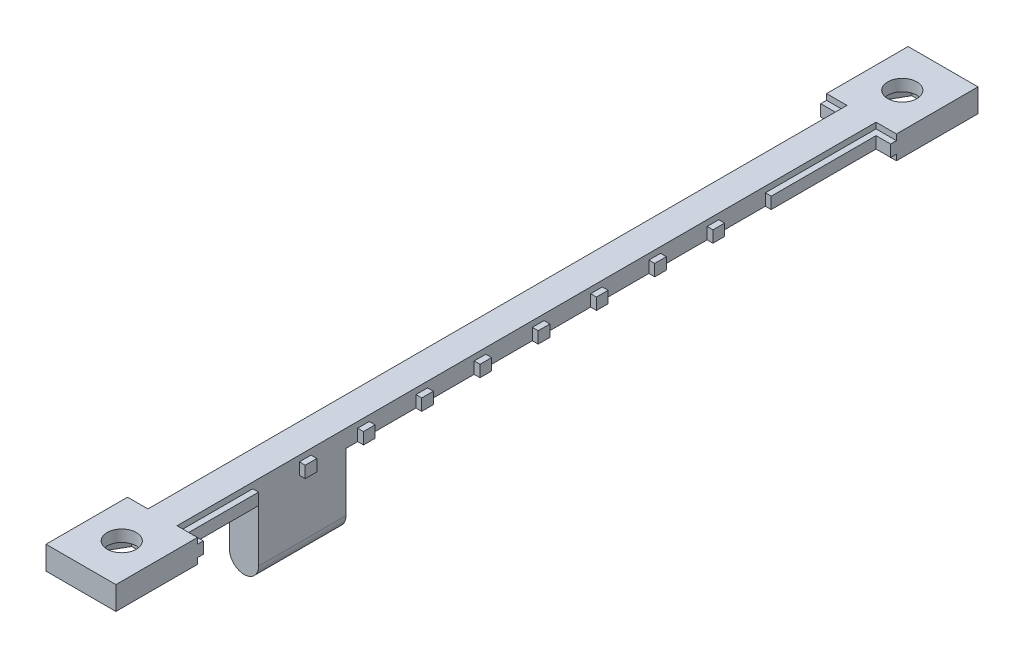
SolidWorks part; units mm, degrees
ref_plane "Front Plane" through (0, 0, 0) normal (0, 0, 1) x (1, 0, 0)
ref_plane "Top Plane" through (0, 0, 0) normal (0, 1, 0) x (1, 0, 0)
ref_plane "Right Plane" through (0, 0, 0) normal (1, 0, 0) x (0, 0, -1)
sketch "Sketch1" plane through (0, 0, 0) normal (0, 1, 0) x (1, 0, 0)
  line L0 (7.2267, 6.096) -> (7.2267, 18.096)
  line L1 (12.2267, 6.096) -> (12.2267, 18.096)
  line L2 (7.2267, 128.096) -> (3.7267, 128.096)
  line L3 (12.2267, 128.096) -> (15.7267, 128.096)
  line L4 (3.7267, 128.096) -> (3.7267, 140.096)
  line L5 (15.7267, 128.096) -> (15.7267, 140.096)
  line L6 (3.7267, 140.096) -> (15.7267, 140.096)
  line L7 (7.2267, 6.096) -> (3.7267, 6.096)
  line L8 (12.2267, 6.096) -> (15.7267, 6.096)
  line L9 (3.7267, 6.096) -> (3.7267, -5.904)
  line L10 (15.7267, 6.096) -> (15.7267, -5.904)
  line L11 (3.7267, -5.904) -> (15.7267, -5.904)
  line L12 (7.2267, 120.096) -> (7.2267, 128.096)
  line L13 (7.2267, 6.096) -> (7.2267, 128.096) construction
  line L14 (-994.5233, 128.096) -> (49005.4767, 128.096) construction
  line L15 (6.2267, 120.096) -> (7.2267, 120.096)
  line L18 (6.2267, 118.096) -> (7.2267, 118.096)
  line L19 (6.2267, 110.096) -> (7.2267, 110.096)
  line L20 (6.2267, 108.096) -> (7.2267, 108.096)
  line L21 (6.2267, 100.096) -> (7.2267, 100.096)
  line L22 (6.2267, 98.096) -> (7.2267, 98.096)
  line L23 (6.2267, 90.096) -> (7.2267, 90.096)
  line L24 (6.2267, 88.096) -> (7.2267, 88.096)
  line L25 (6.2267, 80.096) -> (7.2267, 80.096)
  line L26 (6.2267, 78.096) -> (7.2267, 78.096)
  line L27 (6.2267, 70.096) -> (7.2267, 70.096)
  line L28 (6.2267, 68.096) -> (7.2267, 68.096)
  line L29 (6.2267, 60.096) -> (7.2267, 60.096)
  line L30 (6.2267, 58.096) -> (7.2267, 58.096)
  line L31 (6.2267, 50.096) -> (7.2267, 50.096)
  line L32 (6.2267, 48.096) -> (7.2267, 48.096)
  line L33 (6.2267, 40.096) -> (7.2267, 40.096)
  line L34 (6.2267, 38.096) -> (7.2267, 38.096)
  line L35 (6.2267, 30.096) -> (7.2267, 30.096)
  line L36 (6.2267, 28.096) -> (7.2267, 28.096)
  line L37 (6.2267, 20.096) -> (7.2267, 20.096)
  line L38 (6.2267, 18.096) -> (7.2267, 18.096)
  line L39 (-994.5233, 118.096) -> (49005.4767, 118.096) construction
  line L40 (-994.5233, 120.096) -> (49005.4767, 120.096) construction
  line L41 (12.2267, 120.096) -> (12.2267, 128.096)
  line L42 (12.2267, 6.096) -> (12.2267, 128.096) construction
  line L43 (6.2267, 118.096) -> (6.2267, 120.096)
  line L44 (12.2267, 118.096) -> (13.2267, 118.096)
  line L45 (12.2267, 120.096) -> (13.2267, 120.096)
  line L46 (7.2267, 110.096) -> (7.2267, 118.096)
  line L47 (12.2267, 110.096) -> (12.2267, 118.096)
  line L48 (13.2267, 118.096) -> (13.2267, 120.096)
  line L49 (-994.5233, 110.096) -> (49005.4767, 110.096) construction
  line L50 (-994.5233, 108.096) -> (49005.4767, 108.096) construction
  line L51 (13.2267, 108.096) -> (13.2267, 110.096)
  line L52 (-994.5233, 100.096) -> (49005.4767, 100.096) construction
  line L53 (12.2267, 110.096) -> (13.2267, 110.096)
  line L54 (12.2267, 108.096) -> (13.2267, 108.096)
  line L55 (12.2267, 100.096) -> (13.2267, 100.096)
  line L56 (12.2267, 98.096) -> (13.2267, 98.096)
  line L57 (-994.5233, 98.096) -> (49005.4767, 98.096) construction
  line L58 (12.2267, 90.096) -> (13.2267, 90.096)
  line L59 (-994.5233, 90.096) -> (49005.4767, 90.096) construction
  line L60 (12.2267, 88.096) -> (13.2267, 88.096)
  line L61 (-994.5233, 88.096) -> (49005.4767, 88.096) construction
  line L62 (12.2267, 80.096) -> (13.2267, 80.096)
  line L63 (-994.5233, 80.096) -> (49005.4767, 80.096) construction
  line L64 (12.2267, 78.096) -> (13.2267, 78.096)
  line L65 (-994.5233, 78.096) -> (49005.4767, 78.096) construction
  line L66 (12.2267, 70.096) -> (13.2267, 70.096)
  line L67 (-994.5233, 70.096) -> (49005.4767, 70.096) construction
  line L68 (12.2267, 68.096) -> (13.2267, 68.096)
  line L69 (-994.5233, 68.096) -> (49005.4767, 68.096) construction
  line L70 (12.2267, 60.096) -> (13.2267, 60.096)
  line L71 (-994.5233, 60.096) -> (49005.4767, 60.096) construction
  line L72 (12.2267, 58.096) -> (13.2267, 58.096)
  line L73 (-994.5233, 58.096) -> (49005.4767, 58.096) construction
  line L74 (12.2267, 50.096) -> (13.2267, 50.096)
  line L75 (-994.5233, 50.096) -> (49005.4767, 50.096) construction
  line L76 (12.2267, 48.096) -> (13.2267, 48.096)
  line L77 (-994.5233, 48.096) -> (49005.4767, 48.096) construction
  line L78 (12.2267, 40.096) -> (13.2267, 40.096)
  line L79 (-994.5233, 40.096) -> (49005.4767, 40.096) construction
  line L80 (12.2267, 38.096) -> (13.2267, 38.096)
  line L81 (-994.5233, 38.096) -> (49005.4767, 38.096) construction
  line L82 (12.2267, 30.096) -> (13.2267, 30.096)
  line L83 (-994.5233, 30.096) -> (49005.4767, 30.096) construction
  line L84 (12.2267, 28.096) -> (13.2267, 28.096)
  line L85 (-994.5233, 28.096) -> (49005.4767, 28.096) construction
  line L86 (12.2267, 20.096) -> (13.2267, 20.096)
  line L87 (-994.5233, 20.096) -> (49005.4767, 20.096) construction
  line L88 (12.2267, 18.096) -> (13.2267, 18.096)
  line L89 (-994.5233, 18.096) -> (49005.4767, 18.096) construction
  line L90 (13.2267, 18.096) -> (13.2267, 20.096)
  line L91 (6.2267, 108.096) -> (6.2267, 110.096)
  line L92 (12.2267, 100.096) -> (12.2267, 108.096)
  line L93 (7.2267, 100.096) -> (7.2267, 108.096)
  line L94 (7.2267, 90.096) -> (7.2267, 98.096)
  line L95 (12.2267, 90.096) -> (12.2267, 98.096)
  line L96 (13.2267, 98.096) -> (13.2267, 100.096)
  line L97 (6.2267, 98.096) -> (6.2267, 100.096)
  line L98 (12.2267, 80.096) -> (12.2267, 88.096)
  line L99 (7.2267, 80.096) -> (7.2267, 88.096)
  line L100 (7.2267, 70.096) -> (7.2267, 78.096)
  line L101 (12.2267, 70.096) -> (12.2267, 78.096)
  line L102 (12.2267, 60.096) -> (12.2267, 68.096)
  line L103 (7.2267, 60.096) -> (7.2267, 68.096)
  line L104 (13.2267, 88.096) -> (13.2267, 90.096)
  line L105 (13.2267, 78.096) -> (13.2267, 80.096)
  line L106 (13.2267, 68.096) -> (13.2267, 70.096)
  line L107 (13.2267, 58.096) -> (13.2267, 60.096)
  line L108 (6.2267, 58.096) -> (6.2267, 60.096)
  line L109 (6.2267, 68.096) -> (6.2267, 70.096)
  line L110 (6.2267, 78.096) -> (6.2267, 80.096)
  line L111 (6.2267, 88.096) -> (6.2267, 90.096)
  line L112 (12.2267, 50.096) -> (12.2267, 58.096)
  line L113 (7.2267, 50.096) -> (7.2267, 58.096)
  line L114 (7.2267, 40.096) -> (7.2267, 48.096)
  line L115 (12.2267, 40.096) -> (12.2267, 48.096)
  line L116 (7.2267, 30.096) -> (7.2267, 38.096)
  line L117 (12.2267, 30.096) -> (12.2267, 38.096)
  line L118 (7.2267, 20.096) -> (7.2267, 28.096)
  line L119 (12.2267, 20.096) -> (12.2267, 28.096)
  line L120 (6.2267, 18.096) -> (6.2267, 20.096)
  line L121 (6.2267, 28.096) -> (6.2267, 30.096)
  line L122 (6.2267, 38.096) -> (6.2267, 40.096)
  line L123 (6.2267, 48.096) -> (6.2267, 50.096)
  line L124 (13.2267, 48.096) -> (13.2267, 50.096)
  line L125 (13.2267, 28.096) -> (13.2267, 30.096)
  line L126 (13.2267, 38.096) -> (13.2267, 40.096)
  point P20 (5.4767, 128.096)
  dimension "D1" = 5
  dimension "D4" = 8
  dimension "D5" = 2
  dimension "D6" = 10
  dimension "D7" = 20
  dimension "D8" = 40
  dimension "D9" = 40
extrude "Boss-Extrude1" add sketch "Sketch1" along normal blind 2
sketch "Sketch2" plane through (0, 2, 0) normal (0, 1, 0) x (1, 0, 0)
  line L0 (3.7267, 140.096) -> (15.7267, 140.096)
  line L1 (15.7267, 140.096) -> (15.7267, 128.096)
  line L2 (15.7267, 128.096) -> (12.2267, 128.096)
  line L3 (12.2267, 128.096) -> (15.7267, 128.096) construction
  line L4 (12.2267, 128.096) -> (12.2267, 6.096)
  line L5 (12.2267, 6.096) -> (15.7267, 6.096)
  line L6 (15.7267, 6.096) -> (15.7267, -5.904)
  line L7 (3.7267, -5.904) -> (15.7267, -5.904) construction
  line L8 (15.7267, -5.904) -> (15.7267, 6.096) construction
  line L9 (15.7267, -5.904) -> (3.7267, -5.904)
  line L10 (3.7267, 6.096) -> (3.7267, -5.904) construction
  line L11 (3.7267, -5.904) -> (3.7267, 6.096)
  line L12 (3.7267, 6.096) -> (7.2267, 6.096)
  line L13 (7.2267, 6.096) -> (7.2267, 128.096)
  line L14 (7.2267, 128.096) -> (3.7267, 128.096)
  line L15 (3.7267, 128.096) -> (7.2267, 128.096) construction
  line L16 (3.7267, 140.096) -> (3.7267, 128.096) construction
  line L17 (3.7267, 128.096) -> (3.7267, 140.096)
extrude "Boss-Extrude2" add sketch "Sketch2" along normal blind 1
sketch "Sketch3" plane through (0, 0, 0) normal (0, -1, 0) x (-1, 0, 0)
  line L0 (-15.7267, 128.096) -> (-3.7267, 128.096)
  line L1 (-12.2267, 128.096) -> (-15.7267, 128.096) construction
  line L2 (-15.7267, 128.096) -> (-15.7267, 140.096) construction
  line L3 (-3.7267, 128.096) -> (-3.7267, 140.096)
  line L4 (-3.7267, 140.096) -> (-3.7267, 128.096) construction
  line L5 (-15.7267, 140.096) -> (-3.7267, 140.096) construction
  line L6 (-3.7267, 140.096) -> (-15.7267, 140.096)
  line L7 (-15.7267, 140.096) -> (-15.7267, 128.096)
  line L8 (-3.7267, -5.904) -> (-3.7267, 6.096)
  line L9 (-3.7267, 6.096) -> (-15.7267, 6.096)
  line L10 (-15.7267, 6.096) -> (-15.7267, -5.904)
  line L11 (-15.7267, -5.904) -> (-3.7267, -5.904)
extrude "Boss-Extrude3" add sketch "Sketch3" along normal blind 1 contours L11 L8 L9 L10 | L7 L0 L3 L6
sketch "Sketch4" plane through (0, -1, 0) normal (0, -1, 0) x (-1, 0, 0)
  line L0 (-1015.7267, 134.096) -> (48984.2733, 134.096) construction
  line L1 (-15.7267, 140.096) -> (-15.7267, 128.096) construction
  line L2 (-9.7267, -859.904) -> (-9.7267, 49140.096) construction
  line L3 (-3.7267, 140.096) -> (-15.7267, 140.096) construction
  line L4 (-1015.7267, 0.096) -> (48984.2733, 0.096) construction
  line L11 (-7.3651, 138.096) -> (-11.9839, 138.096)
  line L12 (-11.9839, 138.096) -> (-14.2933, 134.096)
  line L13 (-14.2933, 134.096) -> (-11.9839, 130.096)
  line L14 (-11.9839, 130.096) -> (-7.3651, 130.096)
  line L15 (-7.3651, 130.096) -> (-5.0557, 134.096)
  line L16 (-5.0557, 134.096) -> (-7.3651, 138.096)
  line L17 (-15.7267, 6.096) -> (-15.7267, -5.904) construction
  line L19 (-7.4173, 4.096) -> (-12.0361, 4.096)
  line L20 (-12.0361, 4.096) -> (-14.3455, 0.096)
  line L21 (-14.3455, 0.096) -> (-12.0361, -3.904)
  line L22 (-12.0361, -3.904) -> (-7.4173, -3.904)
  line L23 (-7.4173, -3.904) -> (-5.1079, 0.096)
  line L24 (-5.1079, 0.096) -> (-7.4173, 4.096)
  circle A1 centre (-9.6745, 134.096) radius 4 construction
  circle A2 centre (-9.7267, 0.096) radius 4 construction
  point P5 (-15.7267, 134.096)
  point P10 (-9.7267, 140.096)
  point P31 (-15.7267, 0.096)
extrude "Cut-Extrude1" cut sketch "Sketch4" against normal blind 2 contours L11 L12 L13 L14 L15 L16 | L19 L20 L21 L22 L23 L24
sketch "Sketch5" plane through (0, 1, 0) normal (0, -1, 0) x (-1, 0, 0)
  line L0 (-1005.0557, 134.096) -> (48994.9443, 134.096) construction
  line L1 (-1005.1079, 0.096) -> (48994.8921, 0.096) construction
  line L2 (-9.7267, -995.904) -> (-9.7267, 49004.096) construction
  line L3 (-7.4173, 4.096) -> (-12.0361, 4.096) construction
  circle A0 centre (-9.7267, 0.096) radius 2.5
  circle A1 centre (-9.7267, 134.096) radius 2.5
  point P11 (-9.7267, 4.096)
extrude "Cut-Extrude2" cut sketch "Sketch5" against normal blind 5 contours A1 | A0
sketch "Sketch6" plane through (0, 0, 0) normal (0, -1, 0) x (-1, 0, 0)
  line L0 (-1006.1015, 6.096) -> (48993.8985, 6.096) construction
  line L2 (-1004.9212, 128.096) -> (48995.0788, 128.096) construction
  line L4 (-11.2267, 21.096) -> (-8.2267, 21.096)
  line L5 (-11.2267, 36.096) -> (-8.2267, 36.096)
  line L11 (-12.2267, 21.096) -> (-12.2267, 36.096) construction
  line L14 (-11.2267, 21.096) -> (-11.2267, 36.096)
  line L16 (-8.2267, 21.096) -> (-8.2267, 36.096)
  line L18 (-7.2267, 21.096) -> (-7.2267, 36.096) construction
  line L20 (-1006.1015, 21.096) -> (48993.8985, 21.096) construction
  line L21 (-1006.1015, 36.096) -> (48993.8985, 36.096) construction
  dimension "D1" = 15
  dimension "D2" = 15
extrude "Boss-Extrude4" add sketch "Sketch6" along normal blind 5 contours L4 L16 L5 L14
sketch "Sketch7" plane through (0, 0, -36.096) normal (0, 0, -1) x (-1, 0, 0)
  line L0 (-8.2267, -5) -> (-11.2267, -5)
  line L1 (-11.2267, -5) -> (-11.2267, -1)
  line L2 (-3.7267, -1) -> (-15.7267, -1) construction
  line L3 (-11.2267, -5) -> (-11.2267, 0) construction
  line L4 (-11.2267, -1) -> (-8.2267, -1)
  line L5 (-8.2267, -5) -> (-8.2267, 0) construction
  line L6 (-8.2267, -1) -> (-8.2267, -5)
  ellipse E0 centre (-9.7267, -1) end of major axis (-9.7267, -5) minor radius 1.5 (-11.2267, -1) -> (-8.2267, -1) ccw
  line M2 (-11.2267, 0) -> (-11.2267, -5)
  line M3 (-11.2267, -5) -> (-8.2267, -5)
  line M4 (-8.2267, -5) -> (-8.2267, 0)
extrude "Cut-Extrude3" cut sketch "Sketch7" against normal blind 30 contours E0 L0 M4 | E0 M2 M3 region at (8.5618, -4.1065, -36.096) region at (10.8917, -4.1065, -36.096)
sketch "Sketch8" plane through (0, 0, -36.096) normal (0, 0, -1) x (-1, 0, 0)
  line L0 (-11.2267, -1) -> (-8.2267, -1)
  line L2 (-11.2267, -7) -> (-8.2267, -7)
  line L3 (-11.2267, -1) -> (-11.2267, -7)
  line L4 (-8.2267, -1) -> (-8.2267, -7)
  line L5 (-1008.4727, -7) -> (48991.5273, -7) construction
  line L6 (-1008.4727, -1) -> (48991.5273, -1) construction
  dimension "D1" = 6
sketch "Sketch9" plane through (0, 0, -21.096) normal (0, 0, 1) x (1, 0, 0)
  line L0 (11.2267, 0) -> (11.2267, -7)
  line L1 (11.2267, 0) -> (8.2267, 0)
  line L2 (11.2267, -7) -> (8.2267, -7)
  line L3 (8.2267, -7) -> (8.2267, 0)
extrude "Cut-Extrude5" cut sketch "Sketch9" against normal blind 20 contours L3 L1 L0 L2
sketch "Sketch10" plane through (0, 0, 0) normal (0, -1, 0) x (-1, 0, 0)
  line L0 (-1005.9767, 36.096) -> (48994.0233, 36.096) construction
  line L1 (-3.7267, 6.096) -> (-8.2267, 6.096) construction
  line L2 (-7.2267, 21.096) -> (-7.2267, 36.096)
  line L3 (-7.2267, 28.096) -> (-7.2267, 20.096) construction
  line L4 (-12.2267, 21.096) -> (-12.2267, 36.096)
  line L5 (-12.2267, 20.096) -> (-12.2267, 28.096) construction
  line L6 (-12.2267, 21.096) -> (-7.2267, 21.096)
  line L7 (-12.2267, 36.096) -> (-7.2267, 36.096)
  line L8 (-1005.9767, 21.096) -> (48994.0233, 21.096) construction
  point P10 (-7.2267, 24.096)
  point P15 (-12.2267, 24.096)
  dimension "D2" = 15
extrude "Boss-Extrude5" add sketch "Sketch10" along normal blind 3
sketch "Sketch11" plane through (0, 0, -36.096) normal (0, 0, -1) x (-1, 0, 0)
  line L2 (-7.2267, 0) -> (-7.2267, -3)
  line L4 (-12.2267, 0) -> (-12.2267, -3)
  line L11 (-12.2267, 0) -> (-7.2267, 0) construction
  line L12 (-7.2267, -3) -> (-12.2267, -3)
  line L13 (-12.2267, 0) -> (-7.2267, 0)
  circle A0 centre (-9.7267, 0) radius 2.5
  point P11 (-9.7267, -3)
  line M5 (-12.2267, 0) -> (-12.2267, -3)
  line M6 (-12.2267, -3) -> (-7.2267, -3)
  line M7 (-7.2267, -3) -> (-7.2267, 0)
extrude "Cut-Extrude7" cut sketch "Sketch11" against normal blind 20 contours A0 M5 M6 M7 region at (7.285, -1.5, -36.096)
sketch "Sketch12" plane through (0, 0, 0) normal (0, -1, 0) x (-1, 0, 0)
  line L0 (-7.2267, 21.096) -> (-12.2267, 21.096)
  line L1 (-12.2267, 21.096) -> (-12.2267, 36.096)
  line L2 (-12.2267, 36.096) -> (-7.2267, 36.096)
  line L3 (-7.2267, 36.096) -> (-7.2267, 21.096)
extrude "Boss-Extrude7" add sketch "Sketch12" along normal blind 12.5 contours L3 L0 L1 L2
sketch "Sketch13" plane through (0, 0, -36.096) normal (0, 0, -1) x (-1, 0, 0)
  line L0 (-7.2267, -10) -> (-7.2267, -12.5)
  line L1 (-7.2267, -12.5) -> (-12.2267, -12.5)
  line L2 (-12.2267, -10) -> (-7.2267, -10)
  line L3 (-12.2267, -12.5) -> (-12.2267, -10)
  line L4 (-12.2267, -12.5) -> (-12.2267, 0) construction
  arc A0 (-12.2267, -10) -> (-7.2267, -10) centre (-9.7267, -10) ccw
  line M7 (-12.2267, 0) -> (-12.2267, -12.5)
  line M8 (-12.2267, -12.5) -> (-7.2267, -12.5)
  line M9 (-7.2267, -12.5) -> (-7.2267, 0)
extrude "Cut-Extrude9" cut sketch "Sketch13" against normal blind 40 contours A0 L1 M9 | A0 M7 M8 region at (7.7851, -11.9416, -36.096) region at (11.6683, -11.9416, -36.096)
sketch "Sketch14" plane through (0, 0, 0) normal (0, -1, 0) x (-1, 0, 0)
  line L27 (-7.2267, 6.096) -> (-3.7267, 6.096) construction
  line L33 (-12.2267, 128.096) -> (-15.7267, 128.096) construction
  line L35 (-12.2267, 118.096) -> (-12.2267, 120.096)
  line L36 (-12.2267, 120.096) -> (-13.2267, 120.096)
  line L37 (-13.2267, 120.096) -> (-13.2267, 118.096)
  line L38 (-13.2267, 118.096) -> (-12.2267, 118.096)
extrude "Cut-Extrude11" cut sketch "Sketch14" against normal blind 20
sketch "Sketch15" plane through (0, -1, 0) normal (0, -1, 0) x (-1, 0, 0)
  line L0 (-15.7267, 140.096) -> (-3.7267, 140.096)
  line L1 (-3.7267, 140.096) -> (-3.7267, 141.096)
  line L2 (-15.7267, 128.096) -> (-3.7267, 128.096)
  line L3 (-15.7267, 140.096) -> (-15.7267, 141.096)
  line L4 (-15.7267, 6.096) -> (-3.7267, 6.096)
  line L5 (-11.2267, 6.096) -> (-15.7267, 6.096) construction
  line L6 (-15.7267, -5.904) -> (-3.7267, -5.904)
  line L7 (-15.7267, 128.096) -> (-15.7267, 127.096)
  line L8 (-15.7267, -6.904) -> (-3.7267, -6.904)
  line L9 (-15.7267, 6.096) -> (-15.7267, 7.096)
  line L10 (-15.7267, 127.096) -> (-3.7267, 127.096)
  line L11 (-3.7267, 6.096) -> (-3.7267, 7.096)
  line L12 (-3.7267, -5.904) -> (-3.7267, -6.904)
  line L13 (-15.7267, 7.096) -> (-3.7267, 7.096)
  line L14 (-15.7267, -5.904) -> (-15.7267, -6.904)
  line L15 (-15.7267, 141.096) -> (-3.7267, 141.096)
  line L16 (-1012.2485, -6.904) -> (48987.7515, -6.904) construction
  line L17 (-1012.2485, -5.904) -> (48987.7515, -5.904) construction
  line L18 (-1013.4767, 6.096) -> (48986.5233, 6.096) construction
  line L19 (-1013.4767, 7.096) -> (48986.5233, 7.096) construction
  line L20 (-3.7267, 128.096) -> (-3.7267, 127.096)
  line L21 (-1011.8086, 141.096) -> (48988.1914, 141.096) construction
  line L22 (-1011.8086, 140.096) -> (48988.1914, 140.096) construction
  line L23 (-1013.1732, 128.096) -> (48986.8268, 128.096) construction
  line L24 (-1013.1732, 127.096) -> (48986.8268, 127.096) construction
  line L26 (-15.7267, 141.096) -> (-3.7267, 141.096)
  line L27 (-15.7267, 141.096) -> (-15.7267, 140.096)
  line L28 (-15.7267, 140.096) -> (-3.7267, 140.096)
  line L29 (-3.7267, 141.096) -> (-3.7267, 140.096)
  line L30 (-15.7267, 128.096) -> (-3.7267, 128.096)
  line L31 (-15.7267, 128.096) -> (-15.7267, 127.096)
  line L32 (-15.7267, 127.096) -> (-3.7267, 127.096)
  line L33 (-3.7267, 128.096) -> (-3.7267, 127.096)
  point P9 (-13.4767, 6.096)
  line M11 (-3.7267, 140.096) -> (-15.7267, 140.096)
  line M13 (-15.7267, 128.096) -> (-3.7267, 128.096)
  dimension "D1" = 1
  dimension "D2" = 1
extrude "Boss-Extrude13" add sketch "Sketch15" against normal blind 4 contours L15 L3 L1 M11 | L20 L7 L10 M13 | L13 L9 L4 L11 | L6 L14 L8 L12 region at (9.7267, -1, -140.596) region at (9.7267, -1, -127.596) region at (9.7267, -1, -6.596) region at (9.7267, -1, 6.404)
sketch "Sketch16" plane through (0, 0, 0) normal (0, -1, 0) x (-1, 0, 0)
  line L0 (-15.7267, 7.096) -> (-12.2267, 7.096)
  line L1 (-6.2267, 110.096) -> (-7.2267, 110.096)
  line L2 (-15.7267, 127.096) -> (-12.2267, 127.096)
  line L3 (-7.2267, 110.096) -> (-7.2267, 127.096)
  line L4 (-15.7267, 126.096) -> (-13.2267, 126.096)
  line L5 (-6.2267, 110.096) -> (-6.2267, 126.096)
  line L7 (-15.7267, 8.096) -> (-13.2267, 8.096)
  line L8 (-13.2267, 110.096) -> (-13.2267, 126.096)
  line L9 (-15.7267, 127.096) -> (-15.7267, 126.096)
  line L10 (-3.7267, 127.096) -> (-3.7267, 126.096)
  line L11 (-1006.3754, 126.096) -> (48993.6246, 126.096) construction
  line L12 (-1006.3754, 127.096) -> (48993.6246, 127.096) construction
  line L13 (-6.2267, 126.096) -> (-3.7267, 126.096)
  line L14 (-13.2267, 110.096) -> (-12.2267, 110.096)
  line L15 (-12.2267, 110.096) -> (-12.2267, 127.096)
  line L16 (-7.2267, 127.096) -> (-3.7267, 127.096)
  line L17 (-15.7267, 7.096) -> (-15.7267, 8.096)
  line L18 (-3.7267, 7.096) -> (-3.7267, 8.096)
  line L19 (-6.2267, 18.096) -> (-6.2267, 8.096)
  line L20 (-13.2267, 18.096) -> (-13.2267, 8.096)
  line L21 (-13.2267, 18.096) -> (-12.2267, 18.096)
  line L22 (-12.2267, 18.096) -> (-12.2267, 8.096)
  line L23 (-12.2267, 7.096) -> (-12.2267, 18.096) construction
  line L24 (-6.2267, 18.096) -> (-7.2267, 18.096)
  line L25 (-7.2267, 18.096) -> (-7.2267, 8.096)
  line L26 (-7.2267, 18.096) -> (-7.2267, 7.096) construction
  line L27 (-1013.581, 7.096) -> (48986.419, 7.096) construction
  line L28 (-1013.581, 8.096) -> (48986.419, 8.096) construction
  line L29 (-6.2267, 8.096) -> (-3.7267, 8.096)
  line L30 (-12.2267, 8.096) -> (-12.2267, 7.096)
  line L31 (-7.2267, 8.096) -> (-7.2267, 7.096)
  line L32 (-7.2267, 7.096) -> (-3.7267, 7.096)
  dimension "D1" = 1
  dimension "D2" = 1
extrude "Boss-Extrude14" add sketch "Sketch16" against normal blind 2 contours L18 L29 L19 L24 L25 L31 L32 | L0 L30 L22 L21 L20 L7 L17 | L2 L15 L14 L8 L4 L9 | L10 L13 L5 L1 L3 L16
